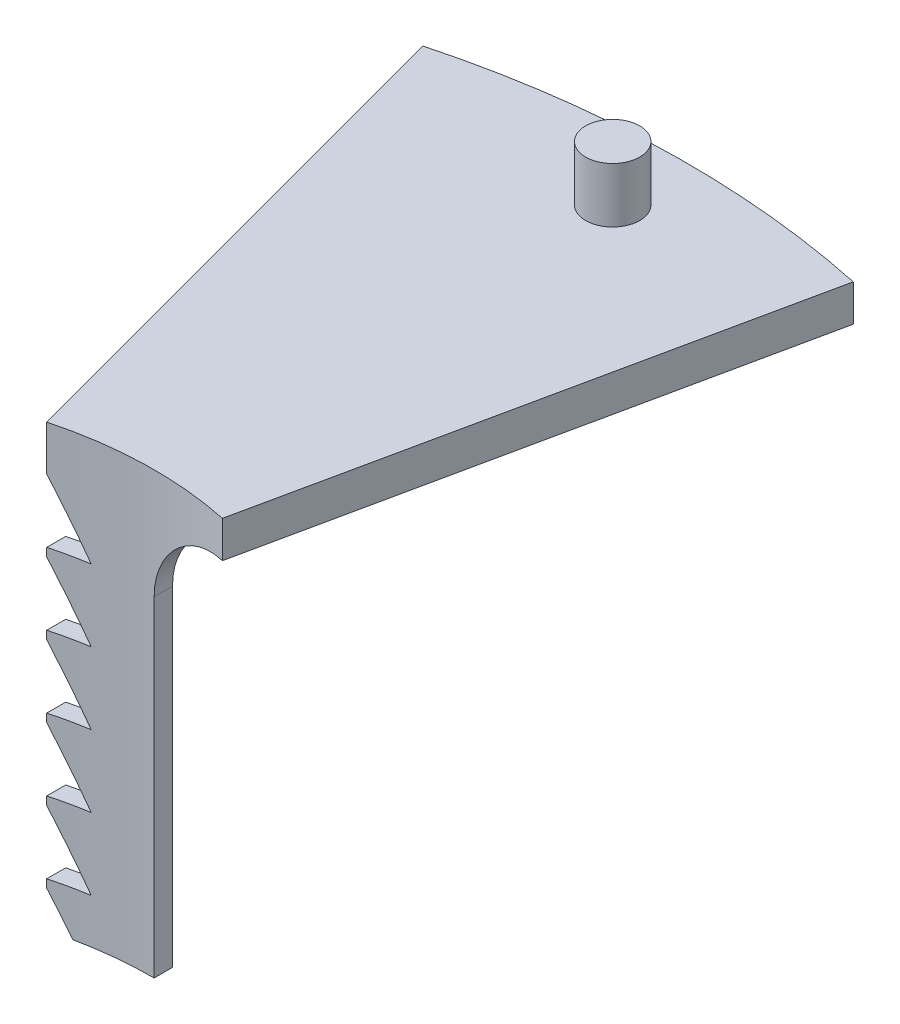
SolidWorks part; units mm, degrees
ref_plane "前视基准面" through (0, 0, 0) normal (0, 0, 1) x (1, 0, 0)
ref_plane "上视基准面" through (0, 0, 0) normal (0, 1, 0) x (1, 0, 0)
ref_plane "右视基准面" through (0, 0, 0) normal (1, 0, 0) x (0, 0, -1)
other "Configuration Table"
sketch "草图1" plane through (0, 0, 0) normal (0, 1, 0) x (1, 0, 0)
  line L0 (4.1582, 19.563) -> (10.1877, 47.9292)
  line L1 (-5.1764, 19.3185) -> (-12.6821, 47.3304)
  line L2 (0, -1000) -> (0, -43) construction
  line L3 (0, -20) -> (0, 0) construction
  line L4 (0, 20) -> (0, 49000) construction
  arc A0 (4.1582, 19.563) -> (-5.1764, 19.3185) centre (0, 0) ccw
  arc A1 (10.1877, 47.9292) -> (-12.6821, 47.3304) centre (0, 0) ccw
  dimension "D1" = 40
  dimension "D2" = 98
  dimension "D3" = 15
  dimension "D4" = 12
extrude "凸台-拉伸1" add sketch "草图1" along normal blind 2
sketch "草图2" plane through (0, 2, 0) normal (0, 1, 0) x (1, 0, 0)
  circle A0 centre (0, 45) radius 1.475
  dimension "D3" = 2.95
extrude "凸台-拉伸2" add sketch "草图2" along normal blind 3
sketch "草图3" plane through (0, 0, 0) normal (0, -1, 0) x (1, 0, 0)
  line L0 (-0.515, -45.4172) -> (0.515, -43.7028) construction
  line L2 (10.1877, -47.9292) -> (4.1582, -19.563)
  line L3 (-5.1764, -19.3185) -> (-12.6821, -47.3304)
  line L7 (0, -1000) -> (0, -42.9046) construction
  line L8 (-1.3293, -44.9279) -> (-0.2993, -43.2135)
  line L9 (0.2993, -45.9065) -> (1.3293, -44.1921)
  arc A2 (-12.6821, -47.3304) -> (10.1877, -47.9292) centre (0, 0) ccw
  arc A3 (-5.1764, -19.3185) -> (4.1582, -19.563) centre (0, 0) ccw
  arc A4 (0, -49) -> (10.1877, -47.9292) centre (0, 0) ccw
  arc A6 (-1.3293, -44.9279) -> (0.2993, -45.9065) centre (-0.515, -45.4172) ccw
  arc A7 (1.3293, -44.1921) -> (-0.2993, -43.2135) centre (0.515, -43.7028) ccw
  point P8 (-1.7784, -41.7397)
  point P9 (0, -44.56)
  dimension "D3" = 0.95
  dimension "D2" = 2
  dimension "D4" = 44.56
  dimension "D5" = 31
  dimension "D1" = 0
extrude "凸台-拉伸3" add sketch "草图3" along normal blind 3 contours L9 A7 L8 A6 region at (0, 0, -44.56)
sketch "草图4" plane through (0, 0, 0) normal (0, -1, 0) x (1, 0, 0)
  line L0 (-0.9901, -19.9755) -> (-0.9901, -21.9777)
  line L2 (10.1877, -47.9292) -> (4.1582, -19.563)
  line L3 (-5.1764, -19.3185) -> (-12.6821, -47.3304)
  line L4 (4.5741, -21.5192) -> (4.1582, -19.563)
  arc A0 (-0.9901, -21.9777) -> (4.5741, -21.5192) centre (0, 0) ccw
  arc A2 (-12.6821, -47.3304) -> (10.1877, -47.9292) centre (0, 0) ccw
  arc A3 (-5.1764, -19.3185) -> (4.1582, -19.563) centre (0, 0) ccw
  arc A4 (-12.6821, -47.3304) -> (10.1877, -47.9292) centre (0, 0) ccw
  arc A5 (-0.9901, -19.9755) -> (4.1582, -19.563) centre (0, 0) ccw
  dimension "D2" = 44
  dimension "D1" = 0
sketch "草图5" plane through (0, 0, 0) normal (0, -1, 0) x (1, 0, 0)
  line L0 (4.1582, -19.563) -> (10.1877, -47.9292) construction
  line L1 (-12.6821, -47.3304) -> (-5.1764, -19.3185) construction
  line L2 (4.1582, -19.563) -> (4.3661, -20.5411)
  line L3 (-5.4352, -20.2844) -> (-5.1764, -19.3185)
  line L4 (0, -20) -> (0, -21)
  arc A0 (-5.4352, -20.2844) -> (4.3661, -20.5411) centre (0, 0) ccw
  arc A1 (-5.1764, -19.3185) -> (4.1582, -19.563) centre (0, 0) ccw construction
  arc A2 (-5.1764, -19.3185) -> (4.1582, -19.563) centre (0, 0) ccw
  arc M10 (4.1582, -19.563) -> (-5.1764, -19.3185) centre (0, 0) cw
  line M11 (-5.1764, -19.3185) -> (-12.6821, -47.3304)
  dimension "D1" = 42
  dimension "D2" = 15
extrude "凸台-拉伸4" add sketch "草图5" along normal blind 22 contours A0 L4 M11 M10 region at (-2.6687, 0, -20.2706)
fillet "圆角1" radius 4 1 edges at (0, 0, -20.5) type face fillet first side face at (0, -11, -20.5) second side face at (0, 0, -44.56)
sketch "草图6" plane through (0, 0, 0) normal (0, 0, 1) x (1, 0, 0)
  line L0 (-12.6821, 0) -> (10.1877, 0) construction
  line L1 (-5.4352, -22) -> (0, -22) construction
  line L2 (-5.4352, -22) -> (-5.4352, 0) construction
  line L3 (-5.1764, -22) -> (0, -22) construction
  line L4 (-5.1764, 2) -> (-5.1764, -22) construction
  line L5 (-12.6821, 0) -> (10.1877, 0)
  line L6 (-5.4352, -22) -> (0, -22)
  line L7 (-5.4352, -22) -> (-5.4352, 0)
  line L8 (-5.1764, -22) -> (0, -22)
  line L9 (-5.1764, 2) -> (-5.1764, -22)
  line L10 (-3.1764, -1004.5016) -> (-3.1764, -11.7372) construction
  line L11 (-5.4352, 0) -> (-3.1764, -3.9124)
  line L12 (-3.1764, -3.9124) -> (-5.4352, -3.9124)
  line L13 (-5.4352, -3.9124) -> (-3.1764, -7.8248)
  line L14 (-3.1764, -7.8248) -> (-5.4352, -7.8248)
  line L15 (-5.4352, -7.8248) -> (-3.1764, -11.7372)
  line L16 (-3.1764, -11.7372) -> (-5.4352, -11.7372)
  line L17 (-5.4352, -11.7372) -> (-3.1764, -15.6496)
  line L18 (-3.1764, -15.6496) -> (-5.4352, -15.6496)
  line L19 (-5.4352, -15.6496) -> (-3.1764, -19.5619)
  line L20 (-3.1764, -7.8248) -> (-3.1764, 48995.4984) construction
  line L21 (-3.1764, -19.5619) -> (-5.4352, -19.5619)
  line L22 (-5.4352, -19.5619) -> (-4.0276, -22)
  dimension "D1" = 2
  dimension "D2" = 60
  dimension "D3" = 60
  dimension "D4" = 60
  dimension "D5" = 60
  dimension "D6" = 60
extrude "切除-拉伸2" cut sketch "草图6" against normal through all and the other way through all contours L22 L9 L6 | L22 L7 L6 L9 | L21 L22 L9 | L21 L19 L9 | L21 L9 L19 L7 | L18 L9 L17 L7 | L18 L17 L9 | L18 L19 L9 | L16 L15 L9 | L16 L9 L15 L7 | L16 L17 L9 | L14 L13 L9 | L14 L9 L13 L7 | L14 L15 L9 | L12 L11 L9 | L12 L9 L11 L7 | L12 L13 L9 | L5 L11 L9 region at (-5.3084, -2.066, 0) region at (-5.2627, -0.1494, 0) region at (-5.3084, -5.9784, 0) region at (-5.2627, -4.0618, 0) region at (-4.5097, -2.7577, 0) region at (-5.3084, -9.8908, 0) region at (-5.2627, -7.9742, 0) region at (-4.5097, -6.6701, 0) region at (-5.3084, -13.8032, 0) region at (-5.2627, -11.8866, 0) region at (-4.5097, -10.5825, 0) region at (-5.3084, -17.7156, 0) region at (-5.2627, -15.799, 0) region at (-4.5097, -14.4949, 0) region at (-5.3102, -20.8893, 0) region at (-5.2627, -19.7114, 0) region at (-4.5097, -18.4072, 0) region at (-4.7935, -21.3367, 0)
fillet "圆角2" radius 1 1 edges at (-0.6028, 0, -20.9913) type face fillet first side face at (-3.7726, -10.7716, -20.5844) second side face at (-0.1056, 0, -28.0808)
